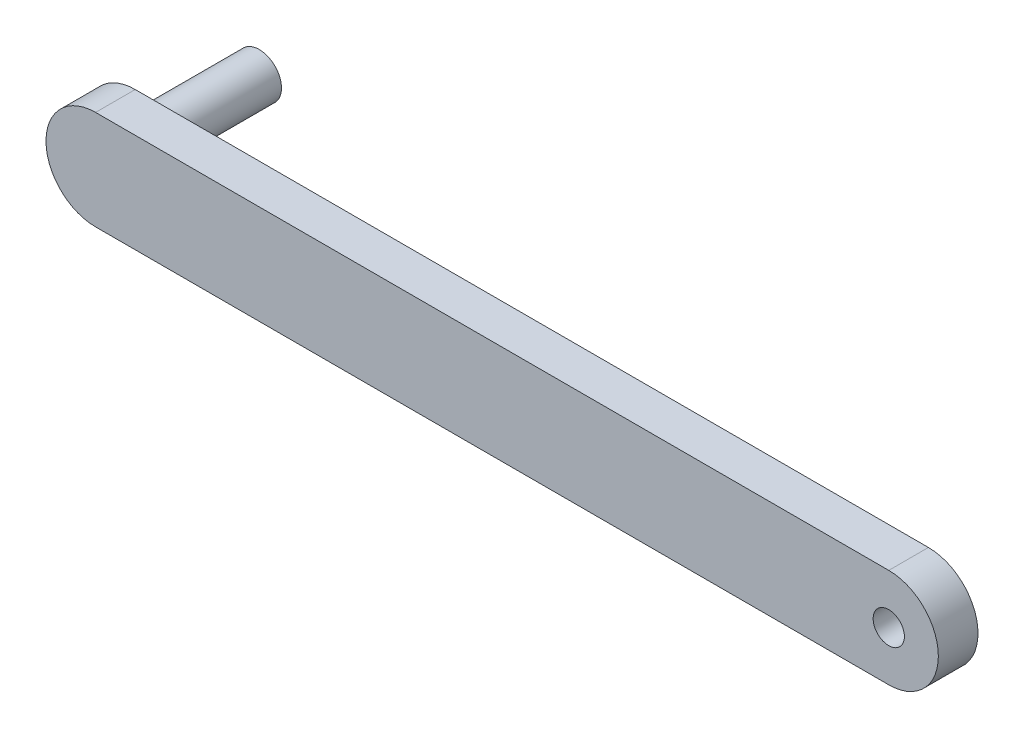
SolidWorks part; units mm, degrees
ref_plane "Front Plane" through (0, 0, 0) normal (0, 0, 1) x (1, 0, 0)
ref_plane "Top Plane" through (0, 0, 0) normal (0, 1, 0) x (1, 0, 0)
ref_plane "Right Plane" through (0, 0, 0) normal (1, 0, 0) x (0, 0, -1)
sketch "Sketch1" plane through (0, 0, 0) normal (0, 0, 1) x (1, 0, 0)
  line L0 (-60, 0) -> (-140, 0) construction
  line L1 (-60, -5) -> (-140, -5)
  line L2 (-60, 5) -> (-140, 5)
  arc A0 (-60, -5) -> (-60, 5) centre (-60, 0) ccw
  arc A1 (-140, 5) -> (-140, -5) centre (-140, 0) ccw
  point P2 (-100, 0)
  dimension "D1" = 10
  dimension "D2" = 80
extrude "Boss-Extrude1" add sketch "Sketch1" along normal blind 4
sketch "Sketch2" plane through (0, 0, 0) normal (0, 0, -1) x (-1, 0, 0)
  circle A0 centre (140, 0) radius 2.25
  dimension "D1" = 4.5
extrude "Boss-Extrude2" add sketch "Sketch2" along normal blind 12.5
fillet "Fillet1" radius 2.5 1 edges at (-137.75, 0, 0)
sketch "Sketch3" plane through (0, 0, -12.5) normal (0, 0, -1) x (-1, 0, 0)
  line L0 (140, -2.25) -> (140, 2.25)
  circle A0 centre (140, 0) radius 2.25 construction
  arc A1 (140, -2.25) -> (140, 2.25) centre (140, 0) ccw
ref_axis "Axis1" through (-140, 0, -12.5) along (0, -1, 0)
sketch "Sketch4" plane through (0, 0, 4) normal (0, 0, 1) x (1, 0, 0)
  circle A0 centre (-60, 0) radius 1.575
  dimension "D1" = 3.15
extrude "Cut-Extrude1" cut sketch "Sketch4" against normal through all
